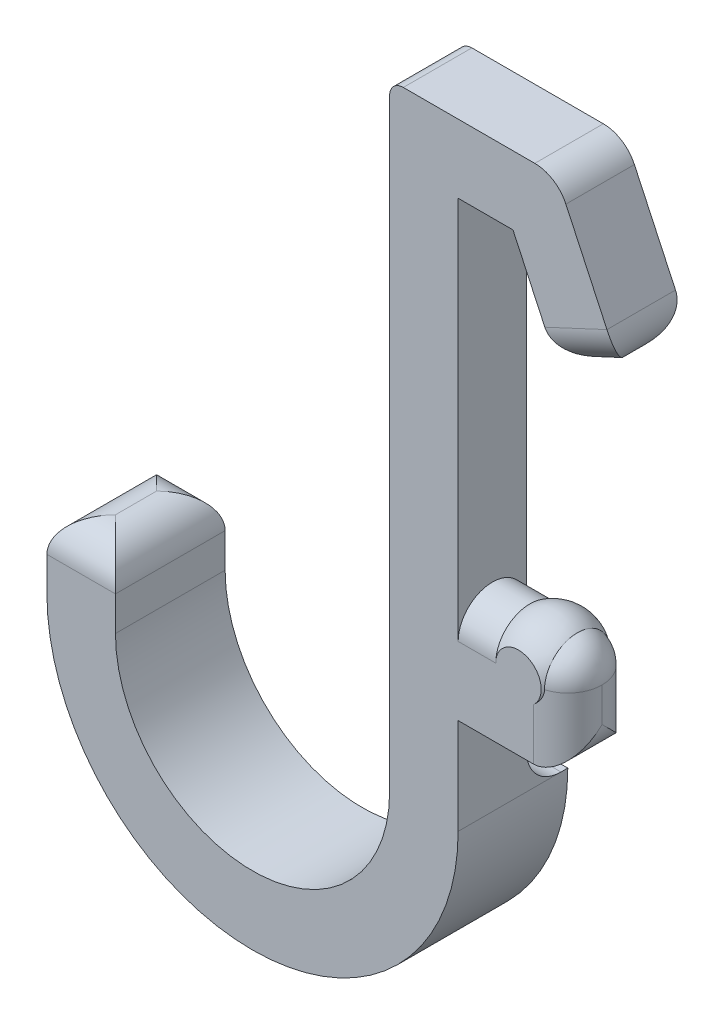
SolidWorks part; units mm, degrees
ref_plane "前视基准面" through (0, 0, 0) normal (0, 0, 1) x (1, 0, 0)
ref_plane "上视基准面" through (0, 0, 0) normal (0, 1, 0) x (1, 0, 0)
ref_plane "右视基准面" through (0, 0, 0) normal (1, 0, 0) x (0, 0, -1)
sketch "草图1" plane through (0, 0, 0) normal (0, 0, 1) x (1, 0, 0)
  line L0 (0, 0) -> (0, 28)
  line L1 (0, 28) -> (4, 28)
  line L2 (4, 28) -> (7.3809, 20.7495)
  line L3 (0, 0) -> (8, 0)
  line L4 (8, 0) -> (8, -5)
  line L5 (8, -5) -> (0, -5)
  line L6 (7.3809, 20.7495) -> (11.9125, 22.8626)
  line L7 (11.9125, 22.8626) -> (7.1854, 33)
  line L8 (-5, 33) -> (7.1854, 33)
  line L9 (-5, 33) -> (-5, -12)
  line L10 (-25, -12) -> (-5, -12) construction
  line L11 (-25, -12) -> (-25, -7)
  line L12 (-25, -7) -> (-30, -7)
  line L13 (-30, -7) -> (-30, -12)
  line L14 (0, -5) -> (0, -12)
  arc A0 (-25, -12) -> (-5, -12) centre (-15, -12) ccw
  arc A1 (-30, -12) -> (0, -12) centre (-15, -12) ccw
  dimension "D11" = 10
  dimension "D1" = 4
  dimension "D2" = 65
  dimension "D3" = 28
  dimension "D4" = 8
  dimension "D5" = 5
  dimension "D6" = 5
  dimension "D7" = 5
  dimension "D8" = 45
  dimension "D9" = 5
  dimension "D10" = 8
  dimension "D12" = 5
  dimension "D13" = 5
extrude "凸台-拉伸1" add sketch "草图1" along normal blind 5
fillet "圆角1" radius 2.5 5 edges at (7.3809, 20.7495, 2.5) (9.6467, 21.8061, 5) (11.9125, 22.8626, 2.5) (9.6467, 21.8061, 0) (7.1854, 33, 2.5)
fillet "圆角2" radius 1 1 edges at (-5, 33, 2.5)
sketch "草图3" plane through (0, 0, 0) normal (1, 0, 0) x (0, 0, -1)
  line L0 (-5, 0) -> (0, 0) construction
  line L1 (-5, 0) -> (0, 0)
  arc A0 (0, 0) -> (-5, 0) centre (-2.5, 0) ccw
extrude "凸台-拉伸2" add sketch "草图3" along normal up to surface (8 mm away) up to face at (8, -2.5, 2.5)
fillet "圆角3" radius 2.5 4 edges at (8, -2.5, 5) (8, -2.5, 0) (8, -5, 2.5) (8, 2.5, 2.5)
ref_plane "基准面1" through (4.4, 0, 0) normal (1, 0, 0) x (0, 0, -1)
sketch "草图4" plane through (4.4, 0, 0) normal (1, 0, 0) x (0, 0, -1)
  line L0 (-2.5, 0) -> (0.5, 0) construction
  line L1 (-5.5, 0) -> (0.5, 0)
  arc A0 (0.5, 0) -> (-5.5, 0) centre (-2.5, 0) ccw
revolve "旋转3" add sketch "草图4" angle 360 about L0
sketch "草图5" plane through (-5, 0, 0) normal (-1, 0, 0) x (0, 0, 1)
  line L0 (0, -2.0992) -> (-1.4678, -2.0992)
  line L1 (0, 32) -> (0, -12) construction
  line L2 (-1.4678, -2.0992) -> (-1.4678, 2.0791)
  line L3 (-1.4678, 2.0791) -> (0, 2.0791)
  line L4 (0, 2.0791) -> (0, -2.0992)
  line L5 (5, -2.0992) -> (6.3896, -2.0992)
  line L6 (5, 32) -> (5, -12) construction
  line L7 (6.3896, -2.0992) -> (6.3896, 2.0791)
  line L8 (6.3896, 2.0791) -> (5, 2.0791)
  line L9 (5, 2.0791) -> (5, -2.0992)
extrude "切除-拉伸1" cut sketch "草图5" against normal blind 20
sketch "草图6" plane through (0, 0, 0) normal (0, 0, -1) x (-1, 0, 0)
  line L0 (25, -12) -> (25, -7) construction
  line L1 (25, -7) -> (30, -7) construction
  line L2 (30, -7) -> (30, -12) construction
  line L3 (25, -7) -> (30, -7)
  line L4 (30, -7) -> (30, -12)
  line L5 (25, -12) -> (25, -7)
  line L6 (0, -12) -> (5, -12)
  arc A0 (5, -12) -> (25, -12) centre (15, -12) ccw construction
  arc A1 (0, -12) -> (30, -12) centre (15, -12) ccw construction
  arc A2 (0, -12) -> (30, -12) centre (15, -12) ccw
  arc A3 (5, -12) -> (25, -12) centre (15, -12) ccw
extrude "凸台-拉伸3" add sketch "草图6" along normal blind 3
fillet "圆角4" radius 2.5 5 edges at (-27.5, -7, 5) (-30, -7, 1) (-27.5, -7, -3) (-25, -7, 1) (-2.5, -12, 0)
